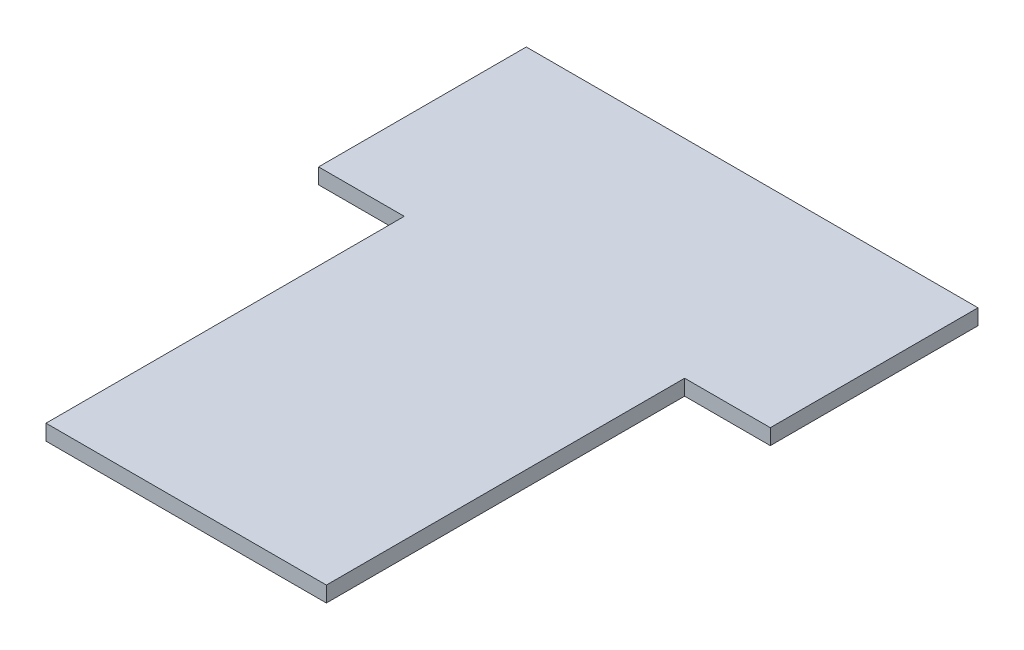
SolidWorks part; units mm, degrees
ref_plane "Front Plane" through (0, 0, 0) normal (0, 0, 1) x (1, 0, 0)
ref_plane "Top Plane" through (0, 0, 0) normal (0, 1, 0) x (1, 0, 0)
ref_plane "Right Plane" through (0, 0, 0) normal (1, 0, 0) x (0, 0, -1)
sketch "Sketch1" plane through (0, 0, 0) normal (0, 1, 0) x (1, 0, 0)
  line L0 (0, 0) -> (87, 0)
  line L1 (87, 0) -> (87, -40)
  line L2 (87, -40) -> (70.5, -40)
  line L3 (70.5, -40) -> (70.5, -109)
  line L4 (70.5, -109) -> (16.5, -109)
  line L5 (16.5, -109) -> (16.5, -40)
  line L6 (16.5, -40) -> (0, -40)
  line L7 (0, -40) -> (0, 0)
  dimension "D1" = 87
  dimension "D2" = 40
  dimension "D3" = 69
  dimension "D4" = 0
  dimension "D5" = 54
extrude "Boss-Extrude1" add sketch "Sketch1" along normal blind 3
